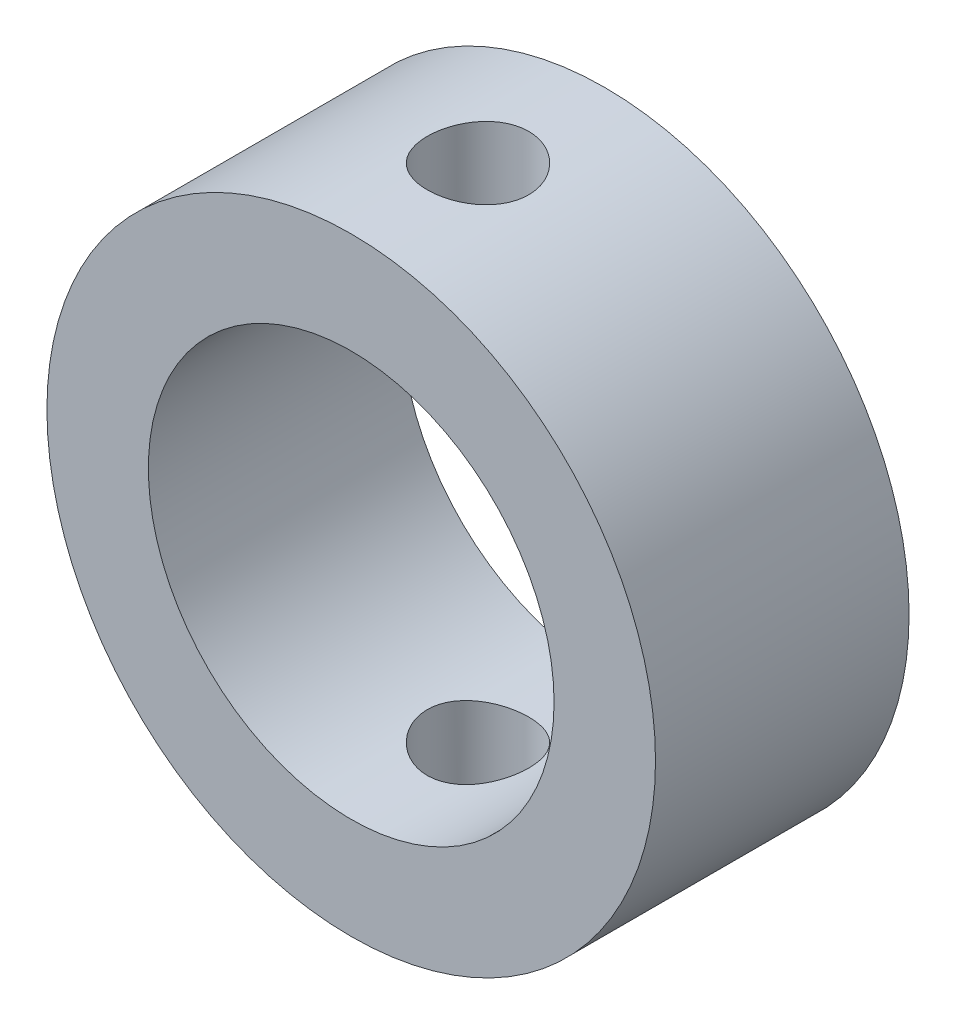
SolidWorks part; units mm, degrees
ref_plane "Plan de face" through (0, 0, 0) normal (0, 0, 1) x (1, 0, 0)
ref_plane "Plan de dessus" through (0, 0, 0) normal (0, 1, 0) x (1, 0, 0)
ref_plane "Plan de droite" through (0, 0, 0) normal (1, 0, 0) x (0, 0, -1)
sketch "Esquisse1" plane through (0, 0, 0) normal (0, 0, 1) x (1, 0, 0)
  circle A0 centre (0, 0) radius 6
  circle A1 centre (0, 0) radius 9
extrude "Boss.-Extru.1" add sketch "Esquisse1" along normal blind 7.5
sketch "Esquisse2" plane through (0, 0, 0) normal (0, 1, 0) x (1, 0, 0)
  line L0 (6, 0) -> (-6, 0) construction
  line L2 (-9, 0) -> (-9, -7.5) construction
  circle A0 centre (0, -3.75) radius 1.5
  dimension "D1" = 3.75
  dimension "D2" = 9
extrude "Enlèv. mat.-Extru.1" cut sketch "Esquisse2" against normal blind 10 and the other way blind 10
